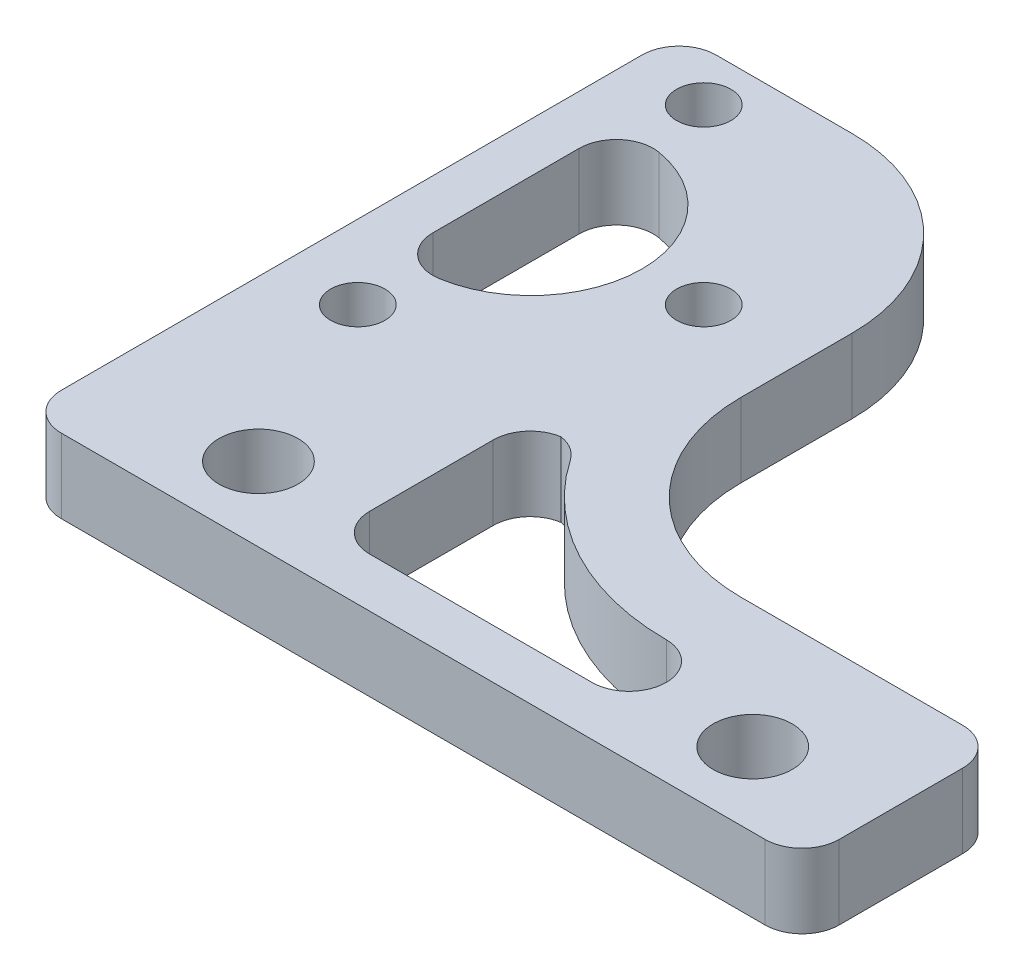
SolidWorks part; units mm, degrees
material "Thornel Mat VMA"
ref_plane "前视基准面" through (0, 0, 0) normal (0, 0, 1) x (1, 0, 0)
ref_plane "上视基准面" through (0, 0, 0) normal (0, 1, 0) x (1, 0, 0)
ref_plane "右视基准面" through (0, 0, 0) normal (1, 0, 0) x (0, 0, -1)
other "Configuration Table"
sketch "草图1" plane through (0, 0, 0) normal (0, 1, 0) x (1, 0, 0)
  line L0 (3.48, -14.5) -> (23.48, -14.5) construction
  line L1 (-3, 9) -> (28.48, 9)
  line L2 (-3, 9) -> (-3, -17.5)
  line L3 (-3, -17.5) -> (28.48, -17.5)
  line L4 (28.48, 9) -> (28.48, -17.5)
  circle A0 centre (0, 0) radius 7 construction
  circle A1 centre (0, 7) radius 1.1
  circle A2 centre (7, 0) radius 1.1
  circle A3 centre (0, -7) radius 1.1
  circle A4 centre (3.48, -14.5) radius 1.6
  circle A5 centre (23.48, -14.5) radius 1.6
  dimension "D1" = 14
  dimension "D2" = 2.2
  dimension "D10" = 3.2
  dimension "D3" = 20
  dimension "D4" = 3
  dimension "D5" = 3
  dimension "D6" = 2
  dimension "D7" = 7.5
  dimension "D8" = 5
  dimension "D9" = 6.48
extrude "凸台-拉伸1" add sketch "草图1" along normal blind 3
sketch "草图2" plane through (0, 3, 0) normal (0, 1, 0) x (1, 0, 0)
  line L0 (28.48, 9) -> (-3, 9) construction
  line L1 (11, 9) -> (28.48, 9)
  line L2 (11, 9) -> (11, -9.5)
  line L3 (11, -9.5) -> (28.48, -9.5)
  line L4 (28.48, 9) -> (28.48, -9.5)
  line L5 (28.48, -17.5) -> (28.48, 9) construction
  line L6 (-3, -17.5) -> (28.48, -17.5) construction
  line L7 (-1, 4.3875) -> (-1, -4.3875)
  line L8 (-3, 9) -> (-3, -17.5) construction
  circle A0 centre (7, 0) radius 1.1 construction
  arc A1 (-1, -4.3875) -> (-1, 4.3875) centre (0, 0) ccw
  dimension "D3" = 9
  dimension "D1" = 8
  dimension "D2" = 4
  dimension "D4" = 2
extrude "切除-拉伸1" cut sketch "草图2" against normal blind 21.5
fillet "圆角1" radius 7 2 edges at (11, 1.5, 9.5) (11, 1.5, -9)
sketch "草图3" plane through (0, 3, 0) normal (0, 1, 0) x (1, 0, 0)
  line L0 (7.48, -7.5) -> (7.48, -15.5)
  line L1 (7.48, -15.5) -> (19.48, -15.5)
  line L2 (19.48, -15.5) -> (19.48, -12.3899)
  line L3 (7.48, -7.5) -> (9.3397, -7.5)
  line L4 (-3, -17.5) -> (28.48, -17.5) construction
  arc A0 (9.3397, -7.5) -> (19.48, -12.3899) centre (18, -2.5) ccw
  circle A7 centre (3.48, -14.5) radius 1.6 construction
  circle A8 centre (23.48, -14.5) radius 1.6 construction
  arc A9 (11, -2.5) -> (18, -9.5) centre (18, -2.5) ccw construction
  dimension "D4" = 3
  dimension "D1" = 2
  dimension "D2" = 4
  dimension "D3" = 4
  dimension "D5" = 8
extrude "切除-拉伸2" cut sketch "草图3" against normal blind 21.5
fillet "圆角2" radius 1.5 11 edges at (28.48, 1.5, 9.5) (-3, 1.5, 17.5) (-3, 1.5, -9) (28.48, 1.5, 17.5) (-1, 1.5, -4.3875) (-1, 1.5, 4.3875) (19.48, 1.5, 12.3899) (19.48, 1.5, 15.5) (7.48, 1.5, 15.5) (9.3397, 1.5, 7.5) (7.48, 1.5, 7.5)
